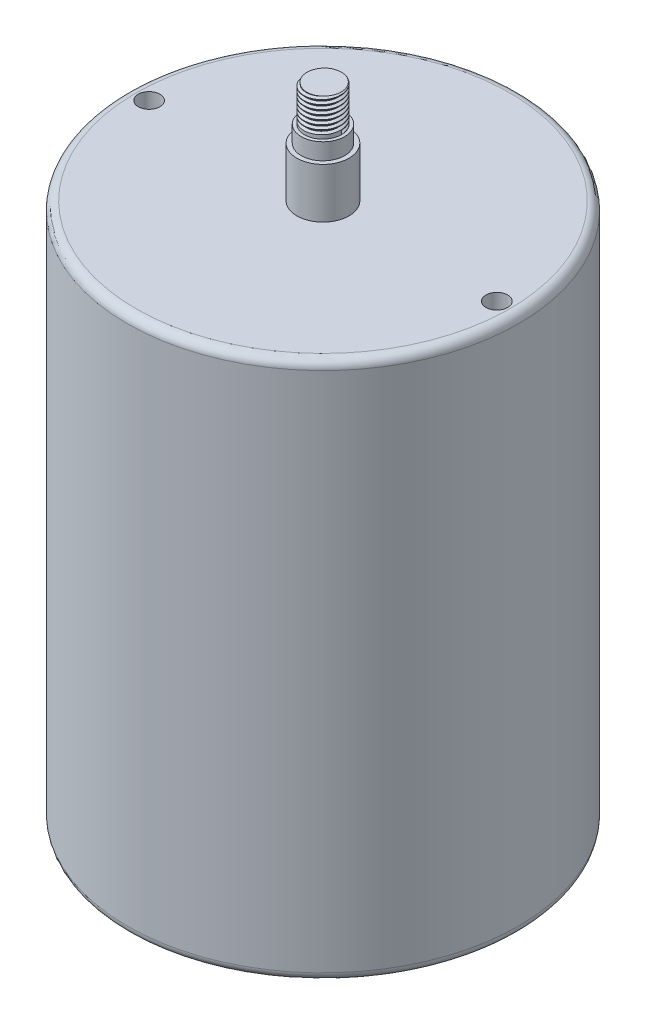
SolidWorks part; units mm, degrees
ref_plane "Front Plane" through (0, 0, 0) normal (0, 0, 1) x (1, 0, 0)
ref_plane "Top Plane" through (0, 0, 0) normal (0, 1, 0) x (1, 0, 0)
ref_plane "Right Plane" through (0, 0, 0) normal (1, 0, 0) x (0, 0, -1)
sketch "Sketch1" plane through (0, 0, 0) normal (0, 1, 0) x (1, 0, 0)
  circle A0 centre (0, 0) radius 45
  dimension "D1" = 90
extrude "Boss-Extrude1" add sketch "Sketch1" along normal blind 124
sketch "Sketch2" plane through (0, 124, 0) normal (0, 1, 0) x (1, 0, 0)
  circle A0 centre (0, 0) radius 6
  dimension "D1" = 12
extrude "Boss-Extrude4" add sketch "Sketch2" along normal blind 11.5 separate body
sketch "Sketch4" plane through (0, 135.5, 0) normal (0, 1, 0) x (1, 0, 0)
  circle A0 centre (0, 0) radius 5
  dimension "D1" = 10
extrude "Boss-Extrude5" add sketch "Sketch4" along normal blind 3.8
sketch "Sketch5" plane through (0, 139.3, 0) normal (0, 1, 0) x (1, 0, 0)
  circle A0 centre (0, 0) radius 4.25
  dimension "D1" = 8.5
extrude "Boss-Extrude6" add sketch "Sketch5" along normal blind 8.2
thread "Thread1" pitch 1 method cut profile "Sketch7" start angle 0, offset 0, length 0, pitch 1, diameter 8.5
ref_plane "Plane1" through (4.25, 139.3, 0) normal (0, 0, 1) x (1, 0, 0)
sketch "Sketch7" plane through (4.25, 139.3, 0) normal (0, 0, 1) x (1, 0, 0)
  line L0 (0, 0) -> (0, 1) construction
  line L11 (0, 0) -> (0, 0.875)
  line L12 (0, 0.875) -> (-0.5413, 0.5625)
  line L13 (-0.5413, 0.5625) -> (-0.5413, 0.3125)
  line L15 (-0.5413, 0.3125) -> (0, 0)
  line L17 (-0.5413, 0.4375) -> (0, 0.4375) construction
  point P2 (0, 0)
  dimension "Pitch" = 1
  dimension "Profile_Angle" = 60
  dimension "Profile_Land" = 0.25
  dimension "Profile_Height" = 0.5413
sketch "Sketch11" plane through (0, 124, 0) normal (0, 1, 0) x (1, 0, 0)
  line L0 (-40, 0) -> (40, 0) construction
  point P4 (0, 0)
  dimension "D1" = 80
hole_wizard "Tap Drill for M6 Tap2" positions "Sketch20" profile "Sketch22" hole size "M6" standard "ISO" end condition through all
sketch "Sketch20" plane through (0, 124, 0) normal (0, 1, 0) x (1, 0, 0)
  point P0 (-40, 0)
  point P3 (40, 0)
sketch "Sketch22" plane through (-40, 124, 0) normal (1, 0, 0) x (0, 0, 1)
  line L0 (0, 0) -> (0, 124)
  line L1 (0, 124) -> (2.5, 124)
  line L2 (2.5, 124) -> (2.5, 0)
  line L5 (2.5, 0) -> (0, 0)
  line L11 (0, -6.35) -> (0, 107.95) construction
  dimension "Thru Hole Dia." = 5
  dimension "Thru Hole Depth" = 124
fillet "Fillet1" radius 2 2 edges at (0, 0, 45) (0, 124, 45)
